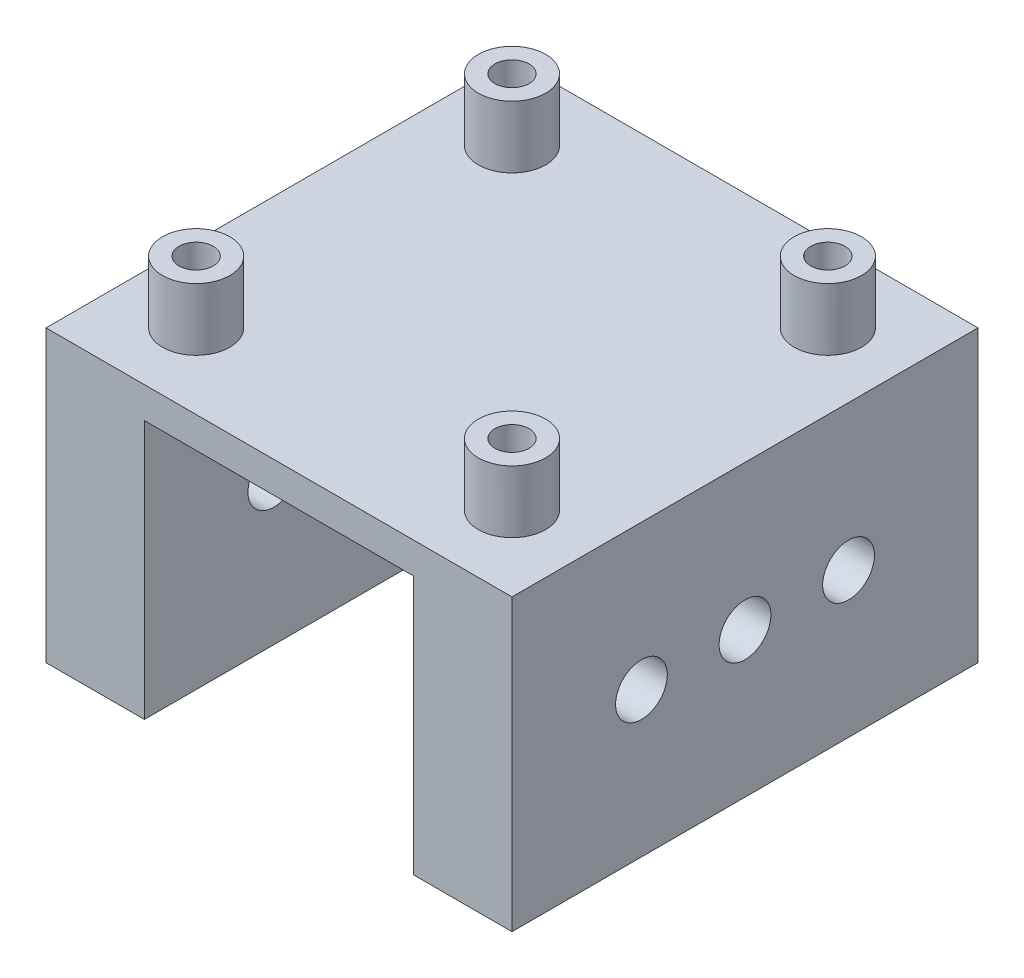
SolidWorks part; units mm, degrees
other "Markup1"
sketch "Sketch6" plane through (-22.5, -3, -30) normal (-0.6806, -0.6949, -0.2324) x (-0.417, 0.1066, 0.9026)
ref_plane "Front Plane" through (0, 0, 0) normal (0, 0, 1) x (1, 0, 0)
ref_plane "Top Plane" through (0, 0, 0) normal (0, 1, 0) x (1, 0, 0)
ref_plane "Right Plane" through (0, 0, 0) normal (1, 0, 0) x (0, 0, -1)
sketch "Sketch1" plane through (0, 0, 0) normal (0, 1, 0) x (1, 0, 0)
  line L7 (15.25, 15.25) -> (-15.25, 15.25) construction
  line L8 (15.25, 15.25) -> (15.25, -15.25) construction
  line L9 (15.25, -15.25) -> (-15.25, -15.25) construction
  line L10 (-15.25, 15.25) -> (-15.25, -15.25) construction
  line L11 (15.25, 15.25) -> (-15.25, -15.25) construction
  line L12 (15.25, -15.25) -> (-15.25, 15.25) construction
  circle A0 centre (-15.25, 15.25) radius 1.65
  circle A1 centre (-15.25, 15.25) radius 3.25
  circle A2 centre (15.25, 15.25) radius 1.65
  circle A3 centre (15.25, 15.25) radius 3.25
  circle A4 centre (15.25, -15.25) radius 1.65
  circle A5 centre (15.25, -15.25) radius 3.25
  circle A6 centre (-15.25, -15.25) radius 1.65
  circle A7 centre (-15.25, -15.25) radius 3.25
  point P0 (0, 0)
  point P18 (0, 0)
  dimension "D4" = 6.5
  dimension "D5" = 3.3
  dimension "D11" = 30.5
  dimension "D12" = 30.5
extrude "Boss-Extrude1" add sketch "Sketch1" along normal blind 6
sketch "Sketch2" plane through (0, 0, 0) normal (0, 1, 0) x (1, 0, 0)
  line L1 (-22.5, -22.5) -> (22.5, -22.5)
  line L2 (-22.5, -22.5) -> (-22.5, 22.5)
  line L3 (-22.5, 22.5) -> (22.5, 22.5)
  line L4 (22.5, -22.5) -> (22.5, 22.5)
  line L5 (-22.5, -22.5) -> (22.5, 22.5) construction
  line L6 (-22.5, 22.5) -> (22.5, -22.5) construction
  point P0 (0, 0)
  dimension "D1" = 45
  dimension "D2" = 45
extrude "Boss-Extrude2" add sketch "Sketch2" against normal blind 3
extrude "Cut-Extrude1" cut sketch "Sketch1<2>" against normal blind 3 contours A0 | A6 | A4 | A2 region at (-15.25, 0, -15.25) region at (-15.25, 0, 15.25)
sketch "Sketch1<2>" plane through (0, 0, 0) normal (0, 1, 0) x (1, 0, 0) same geometry as "Sketch1"
sketch "Sketch7" plane through (0, -3, 0) normal (0, -1, 0) x (1, 0, 0)
  line L0 (-22.5, 22.5) -> (22.5, 22.5) construction
  line L2 (-13, 22.5) -> (-13, -22.5)
  line L3 (22.5, -22.5) -> (-22.5, -22.5) construction
  line L4 (13, 22.5) -> (13, -22.5)
  line L5 (13, -22.5) -> (22.5, -22.5)
  line L6 (22.5, -22.5) -> (22.5, 22.5)
  line L7 (22.5, 22.5) -> (13, 22.5)
  line L8 (-13, 22.5) -> (-22.5, 22.5)
  line L9 (-22.5, 22.5) -> (-22.5, -22.5)
  line L10 (-22.5, -22.5) -> (-13, -22.5)
  dimension "D1" = 9.5
  dimension "D2" = 9.5
extrude "Boss-Extrude3" add sketch "Sketch7" along normal blind 25 contours L10 L2 L8 L9 | L7 L4 L5 L6
sketch "Sketch8" plane through (22.5, 0, 0) normal (1, 0, 0) x (0, 0, -1)
  circle A0 centre (0, -14) radius 2.5
  circle A1 centre (-10, -14) radius 2.5
  circle A2 centre (10, -14) radius 2.5
  dimension "D1" = 5
extrude "Cut-Extrude2" cut sketch "Sketch8" against normal through all
